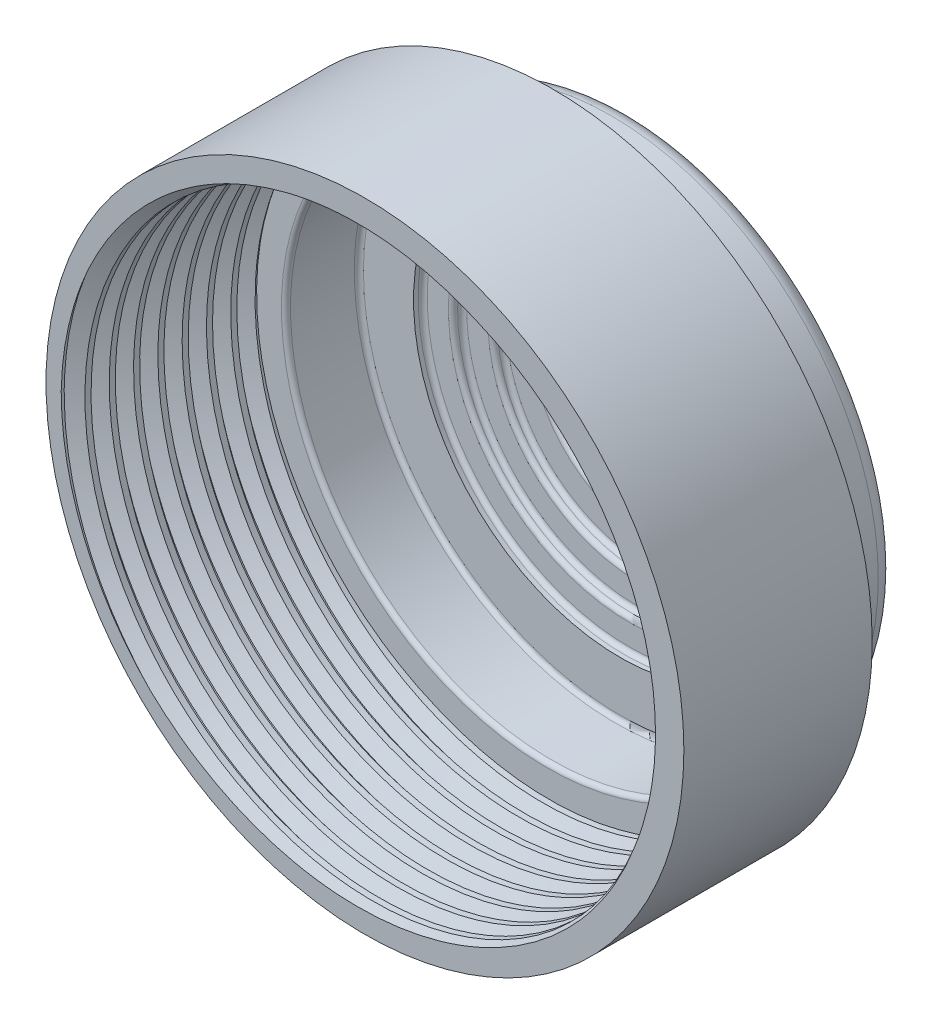
SolidWorks part; units mm, degrees
ref_plane "Plan de face" through (0, 0, 0) normal (0, 0, 1) x (1, 0, 0)
ref_plane "Plan de dessus" through (0, 0, 0) normal (0, 1, 0) x (1, 0, 0)
ref_plane "Plan de droite" through (0, 0, 0) normal (1, 0, 0) x (0, 0, -1)
sketch "Esquisse2" plane through (0, 0, 0) normal (0, 0, 1) x (1, 0, 0)
  circle A0 centre (-150, 595) radius 45 construction
  circle A1 centre (-150, 595) radius 45 construction
  circle A2 centre (-150, 595) radius 52.5
  circle A3 centre (-150, 595) radius 44
  circle A5 centre (-150, 595) radius 43
  circle A6 centre (-150, 595) radius 34
  circle A7 centre (-150, 595) radius 24
  circle A9 centre (-150, 595) radius 16.5
  circle A10 centre (-150, 595) radius 9
  circle A11 centre (-150, 595) radius 39
  circle A12 centre (-150, 595) radius 29
  circle A13 centre (-150, 595) radius 18.5
  circle A14 centre (-150, 595) radius 11
  circle M6 centre (-150, 595) radius 45
  dimension "D1" = 7.5
  dimension "D2" = 1
  dimension "D3" = 1
  dimension "D4" = 9
  dimension "D5" = 10
  dimension "D6" = 7.5
  dimension "D7" = 7.5
  dimension "D8" = 5
  dimension "D9" = 5
  dimension "D10" = 2
  dimension "D11" = 2
extrude "Boss.-Extru.1" add sketch "Esquisse2" along normal blind 1 contours A2 M6 | A3 M6 | A3 region at (-201.0151, 595, 0) region at (-193.8755, 595, 0) region at (-194.8727, 595, 0)
extrude "Boss.-Extru.2" add sketch "Esquisse2<3>" against normal blind 11 contours A3 A5 region at (-193.8755, 595, 0)
sketch "Esquisse2<3>" plane through (0, 0, 0) normal (0, 0, 1) x (1, 0, 0) same geometry as "Esquisse2"
extrude "Boss.-Extru.3" add sketch "Esquisse2<5>" against normal blind 1.5 from surface contours A3 | A6 starting at face at (-107, 595, -11)
sketch "Esquisse2<5>" plane through (0, 0, 0) normal (0, 0, 1) x (1, 0, 0) same geometry as "Esquisse2"
extrude "Boss.-Extru.4" add sketch "Esquisse2<6>" against normal blind 1.5 from surface contours A11 | A12 starting at face at (-116, 595, -12.5)
sketch "Esquisse2<6>" plane through (0, 0, 0) normal (0, 0, 1) x (1, 0, 0) same geometry as "Esquisse2"
extrude "Boss.-Extru.5" add sketch "Esquisse2<7>" against normal blind 1.5 from surface contours A6 | A7 starting at face at (-121, 595, -14)
sketch "Esquisse2<7>" plane through (0, 0, 0) normal (0, 0, 1) x (1, 0, 0) same geometry as "Esquisse2"
extrude "Boss.-Extru.6" add sketch "Esquisse2<8>" against normal blind 1.5 from surface contours A12 | A13 starting at face at (-126, 595, -15.5)
sketch "Esquisse2<8>" plane through (0, 0, 0) normal (0, 0, 1) x (1, 0, 0) same geometry as "Esquisse2"
extrude "Boss.-Extru.7" add sketch "Esquisse2<9>" against normal blind 1.5 from surface contours A7 | A9 starting at face at (-131.5, 595, -17)
sketch "Esquisse2<9>" plane through (0, 0, 0) normal (0, 0, 1) x (1, 0, 0) same geometry as "Esquisse2"
extrude "Boss.-Extru.8" add sketch "Esquisse2<10>" against normal blind 1.5 from surface separate body contours A13 starting at face at (-133.5, 595, -18.5)
sketch "Esquisse2<10>" plane through (0, 0, 0) normal (0, 0, 1) x (1, 0, 0) same geometry as "Esquisse2"
fillet "Congé1" radius 3 5 edges at (-126, 595, -18.5) (-121, 595, -17) (-116, 595, -15.5) (-111, 595, -14) (-106, 595, -12.5)
fillet "Congé2" radius 3 1 edges at (-131.5, 595, -20)
fillet "Congé3" radius 0.75 9 edges at (-133.5, 595, -17) (-131.5, 595, -15.5) (-126, 595, -14) (-121, 595, -12.5) (-107, 595, 1) (-126, 595, -15.5) (-121, 595, -14) (-116, 595, -12.5) (-107, 595, -11)
sketch "Esquisse3" plane through (0, 0, 1) normal (0, 0, 1) x (1, 0, 0)
  circle A0 centre (-150, 595) radius 52.5 construction
  circle A1 centre (-150, 595) radius 52.5
  circle A4 centre (-150, 595) radius 50
  dimension "D1" = 100
extrude "Boss.-Extru.9" add sketch "Esquisse3" along normal blind 30
thread "Filetage1" pitch 4 method extrude trim with start face yes trim with end face yes profile "Profil de filetage2" start angle 0, offset 3.5, length 33.5, pitch 4, diameter 100
ref_plane "Plan2" through (-200, 595, 34.5) normal (0, -1, 0) x (-1, 0, 0)
sketch "Profil de filetage2" plane through (-200, 595, 34.5) normal (0, -1, 0) x (-1, 0, 0)
  line L0 (0, 0) -> (0, 4) construction
  line L11 (0, 0) -> (0, 3.5)
  line L12 (0, 3.5) -> (-2.1651, 2.25)
  line L13 (-2.1651, 2.25) -> (-2.1651, 1.25)
  line L15 (-2.1651, 1.25) -> (0, 0)
  line L17 (-2.1651, 1.75) -> (0, 1.75) construction
  point P2 (0, 0)
  dimension "Pitch" = 4
  dimension "Profile_Angle" = 60
  dimension "Profile_Land" = 1
  dimension "Profile_Height" = 2.1651
